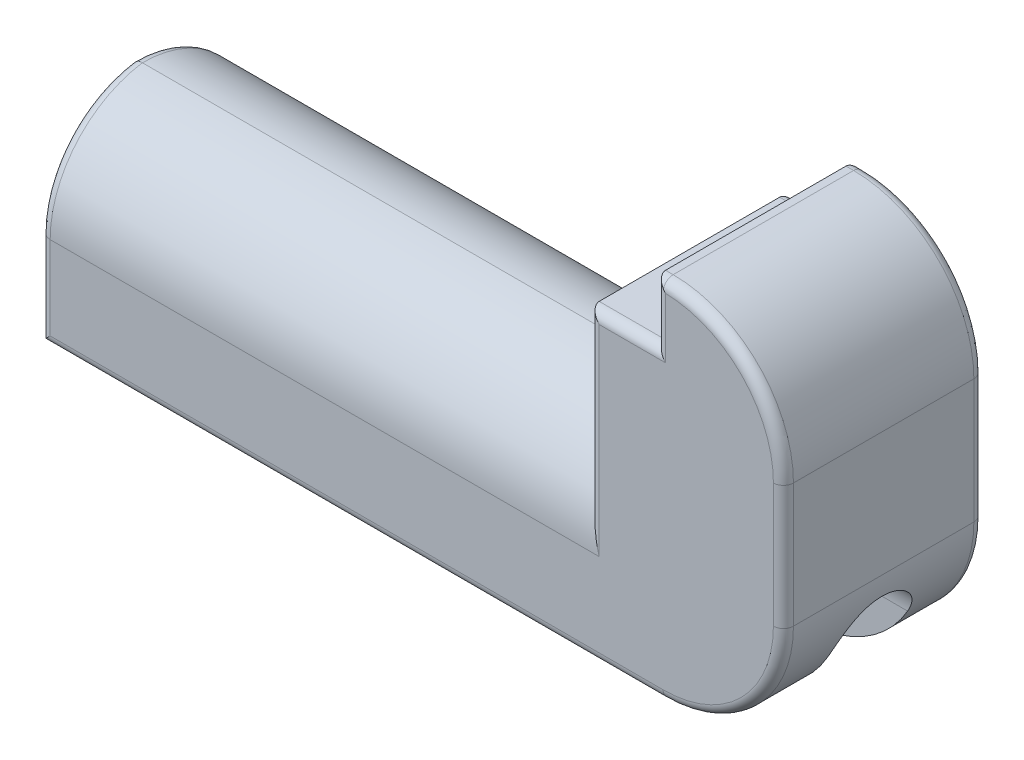
SolidWorks part; units mm, degrees
ref_plane "Front Plane" through (0, 0, 0) normal (0, 0, 1) x (1, 0, 0)
ref_plane "Top Plane" through (0, 0, 0) normal (0, 1, 0) x (1, 0, 0)
ref_plane "Right Plane" through (0, 0, 0) normal (1, 0, 0) x (0, 0, -1)
sketch "Sketch1" plane through (0, 0, 0) normal (0, 0, 1) x (1, 0, 0)
  line L0 (-139.1464, 0) -> (210.8536, 0) construction
  line L2 (-144.0044, -48.147) -> (166.7822, -48.147)
  line L3 (-144.0044, -48.147) -> (-144.0044, 51.853)
  line L4 (-144.0044, 51.853) -> (129.8735, 51.853)
  line L5 (226.7822, 11.853) -> (226.7822, 46.0483)
  line L6 (162.976, 133.7076) -> (166.7822, 133.7076)
  line L7 (129.8735, 103.7076) -> (129.8735, 51.853)
  line L9 (226.7822, 73.7076) -> (226.7822, 46.0483)
  line L12 (129.8735, 103.7076) -> (162.976, 103.7076)
  line L13 (162.976, 133.7076) -> (162.976, 103.7076)
  arc A0 (166.7822, 133.7076) -> (226.7822, 73.7076) centre (166.7822, 73.7076) cw
  arc A1 (166.7822, -48.147) -> (226.7822, 11.853) centre (166.7822, 11.853) ccw
  dimension "D2" = 60
  dimension "D1" = 350
  dimension "D3" = 30
  dimension "D4" = 100
extrude "Boss-Extrude1" add sketch "Sketch1" along normal mid plane 100
fillet "Fillet5" radius 54 1 edges at (-7.0654, 51.853, -50)
fillet "Fillet6" radius 54 1 edges at (-7.0654, 51.853, 50)
fillet "Fillet3" radius 5 18 edges at (129.8735, 51.0782, 50) (146.4248, 103.7076, 50) (162.976, 118.7076, 50) (209.2086, 116.134, 50) (226.7822, 42.7803, 50) (209.2086, -30.5734, 50) (11.3889, -48.147, 50) (-144.0044, -24.849, 50) (11.3889, -48.147, -50) (209.2086, -30.5734, -50) (226.7822, 42.7803, -50) (209.2086, 116.134, -50) (162.976, 118.7076, -50) (146.4248, 103.7076, -50) (129.8735, 50.7803, -50) (-144.0044, -25.147, -50) (-144.0044, 33.6909, 36.9145) (-144.0044, 36.0368, -34.1838)
fillet "Fillet4" [suppressed] radius 5
sketch "Sketch2" plane through (-144.0044, 0, 0) normal (-1, 0, 0) x (0, 0, 1)
  line L0 (0, -48.147) -> (0, 11.853) construction
  line L1 (-20, -18.147) -> (-20, -71.3001)
  line L2 (-20, -71.3001) -> (20, -71.3001)
  line L3 (20, -71.3001) -> (20, -18.147)
  arc A0 (20, -18.147) -> (-20, -18.147) centre (0, -18.147) ccw
  point P0 (0, -9.9322)
  dimension "D1" = 40
extrude "Cut-Extrude1" cut sketch "Sketch2" against normal through all
